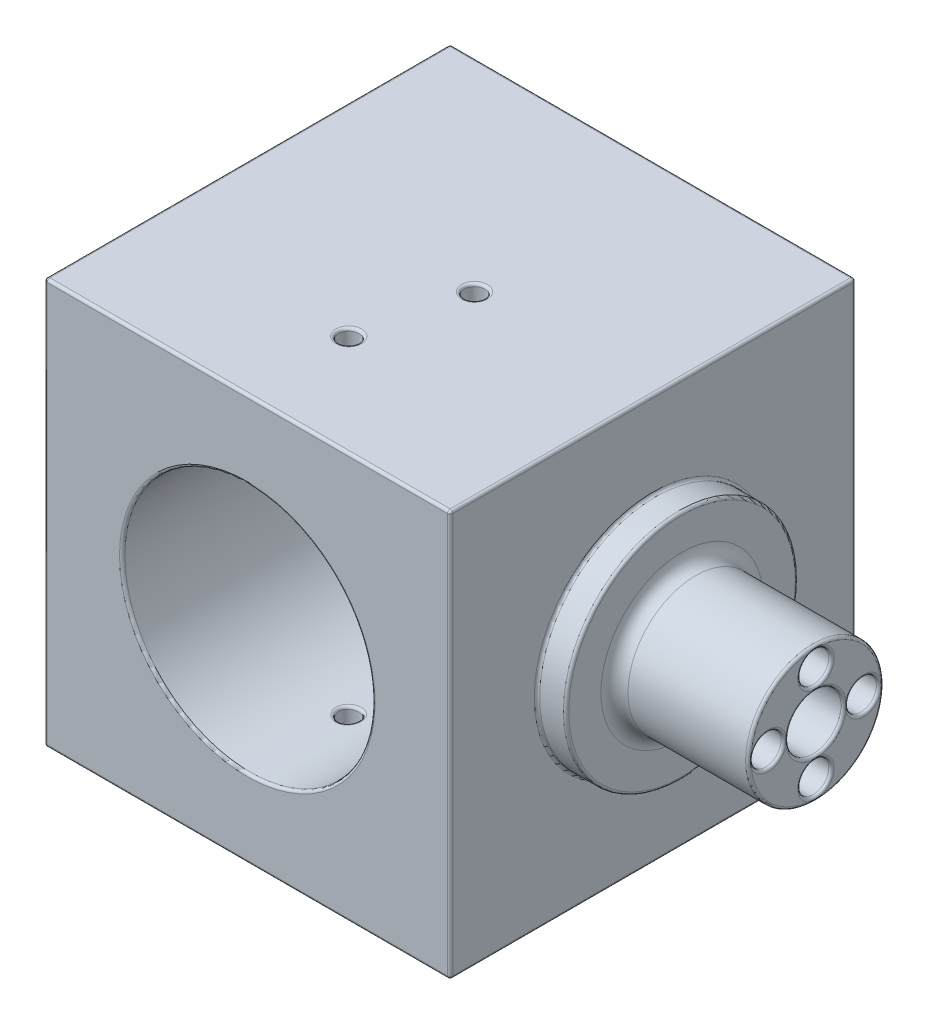
SolidWorks part; units mm, degrees
ref_plane "Front Plane" through (0, 0, 0) normal (0, 0, 1) x (1, 0, 0)
ref_plane "Top Plane" through (0, 0, 0) normal (0, 1, 0) x (1, 0, 0)
ref_plane "Right Plane" through (0, 0, 0) normal (1, 0, 0) x (0, 0, -1)
sketch "Sketch1" plane through (0, 0, 0) normal (0, 0, 1) x (1, 0, 0)
  line L1 (-30, -30) -> (30, -30)
  line L2 (-30, -30) -> (-30, 30)
  line L3 (-30, 30) -> (30, 30)
  line L4 (30, -30) -> (30, 30)
  line L5 (-30, -30) -> (30, 30) construction
  line L6 (-30, 30) -> (30, -30) construction
  point P0 (0, 0)
  dimension "D1" = 60
extrude "Boss-Extrude1" add sketch "Sketch1" along normal mid plane 60
sketch "Sketch2" plane through (0, 0, -30) normal (0, 0, -1) x (-1, 0, 0)
  line L0 (30, -30) -> (-30, 30) construction
  circle A0 centre (0, 0) radius 23.7
  dimension "D1" = 47.4
extrude "Cut-Extrude1" cut sketch "Sketch2" against normal blind 12 contours A0
sketch "Sketch3" plane through (0, 0, -30) normal (0, 0, -1) x (-1, 0, 0)
  line L0 (30, -30) -> (-30, 30) construction
  circle A0 centre (0, 0) radius 18.5
  dimension "D1" = 37
extrude "Cut-Extrude2" cut sketch "Sketch3" against normal through all
sketch "Sketch5" plane through (30, 0, 0) normal (1, 0, 0) x (0, 0, -1)
  line L0 (0, -30) -> (0, 30) construction
  circle A0 centre (0, 0) radius 17.15
  dimension "D1" = 34.3
extrude "Boss-Extrude2" add sketch "Sketch5" along normal blind 4.3
sketch "Sketch6" plane through (34.3, 0, 0) normal (1, 0, 0) x (0, 0, -1)
  line L0 (0, 30) -> (0, -30) construction
  circle A0 centre (0, 0) radius 10
  dimension "D1" = 20
extrude "Boss-Extrude3" add sketch "Sketch6" along normal blind 19.8 contours A0
fillet "Fillet1" radius 2 1 edges at (34.3, 0, -10)
sketch "Sketch7" plane through (54.1, 0, 0) normal (1, 0, 0) x (0, 0, -1)
  circle A0 centre (0, 0) radius 4.1
  dimension "D1" = 8.2
extrude "Cut-Extrude3" cut sketch "Sketch7" against normal blind 19.8
sketch "Sketch8" plane through (54.1, 0, 0) normal (1, 0, 0) x (0, 0, -1)
  line L0 (4.1, 0) -> (7.05, 0) construction
  line L1 (7.05, 0) -> (10, 0) construction
  circle A0 centre (7.05, 0) radius 2.3
  circle A1 centre (0, 0) radius 4.1 construction
  circle A2 centre (0, 0) radius 4.1 construction
  circle A3 centre (0, 0) radius 10 construction
  circle A4 centre (0, 0) radius 10 construction
  circle A5 centre (0, -7.05) radius 2.3
  circle A6 centre (-7.05, 0) radius 2.3
  circle A7 centre (0, 7.05) radius 2.3
  point P23 (0, 0)
  dimension "D1" = 4.6
  dimension "D2" = 4
extrude "Cut-Extrude4" cut sketch "Sketch8" against normal blind 5.7
sketch "Sketch11" plane through (0, -30, 0) normal (0, -1, 0) x (1, 0, 0)
  line L0 (0, -30) -> (0, 0) construction
  line L1 (-30, -30) -> (30, -30) construction
  line L2 (-15.5, -18.2) -> (-15.5, 11.8) construction
  line L3 (-15.5, -18.2) -> (-15.5, -30) construction
  circle A0 centre (-15.5, -18.2) radius 2.8
  circle A1 centre (-15.5, 11.8) radius 2.8
  circle A2 centre (15.5, -18.2) radius 2.8
  circle A3 centre (15.5, 11.8) radius 2.8
  dimension "D1" = 5.6
  dimension "D2" = 30
  dimension "D3" = 15.5
  dimension "D4" = 11.8
extrude "Cut-Extrude5" cut sketch "Sketch11" against normal blind 8
sketch "Sketch12" plane through (0, 30, 0) normal (0, 1, 0) x (1, 0, 0)
  line L2 (30, 0) -> (3.6, 0) construction
  line L3 (30, -17.15) -> (30, 17.15) construction
  line L4 (-33, 0) -> (33, 0) construction
  circle A0 centre (3.6, 0) radius 1.5
  dimension "D2" = 3
  dimension "D3" = 26.4
extrude "Cut-Extrude6" cut sketch "Sketch12" against normal blind 5
sketch "Sketch14" plane through (-30, 0, 0) normal (-1, 0, 0) x (0, 0, 1)
  line L0 (30, 0) -> (3.6, 0) construction
  line L1 (30, 30) -> (30, -30) construction
  circle A0 centre (3.6, 0) radius 1.5
  dimension "D1" = 3
  dimension "D2" = 26.4
extrude "Cut-Extrude7" cut sketch "Sketch14" against normal blind 6
sketch "Sketch16" plane through (0, 30, 0) normal (0, 1, 0) x (1, 0, 0)
  line L1 (30, -30) -> (-30, -30) construction
  line L4 (0, 0) -> (0, -30) construction
  circle A0 centre (0, -15) radius 1.5
  dimension "D1" = 3
extrude "Cut-Extrude9" cut sketch "Sketch16" against normal through all contours A0
fillet "Fillet2" radius 0.4 45 edges at (30, 0, 30) (30, 0, -30) (-30, 0, 30) (-30, 0, -30) (-30, -30, 0) (0, -30, 30) (30, -30, 0) (0, -30, -30) (30, 30, 0) (0, 30, 30) (-30, 30, 0) (0, 30, -30) (-23.7, 0, -30) (-18.5, 0, 30) (-23.7, 0, -18) (-18.5, 0, -18) (30, 0, -17.15) (34.3, 0, -17.15) (54.1, 0, -4.1) (34.3, 0, -4.1) (54.1, 7.05, -2.3) (48.4, 7.05, -2.3) (54.1, 0, 4.75) (48.4, 0, 4.75) (54.1, -7.05, -2.3) (48.4, -7.05, -2.3) (54.1, 0, -10) (54.1, 0, -9.35) (48.4, 0, -9.35) (-15.5, -30, -21) (15.5, -30, 14.6) (15.5, -30, -15.4) (-15.5, -30, 9) (-15.5, -22, -21) (-15.5, -22, 9) (15.5, -22, 14.6) (15.5, -22, -15.4) (3.6, 30, 1.5) (3.6, 25, 1.5) (-30, 0, 5.1) (-24, 0, 5.1) (0, -30, 16.5) (0, 30, 16.5) (0.3395, -18.4969, 13.5389) (-0.3395, 18.4969, 13.5389)
sketch "Sketch9" plane through (0, 0, -30) normal (0, 0, -1) x (-1, 0, 0)
  line L0 (0, 0) -> (0, -58.614) construction
  line L2 (-21, -79.614) -> (21, -79.614) construction
  line L3 (-21, -79.614) -> (-21, -37.614) construction
  line L4 (-21, -37.614) -> (21, -37.614) construction
  line L5 (21, -79.614) -> (21, -37.614) construction
  line L6 (-21, -79.614) -> (21, -37.614) construction
  line L7 (-21, -37.614) -> (21, -79.614) construction
  dimension "D1" = 42
  dimension "D2" = 58.614
